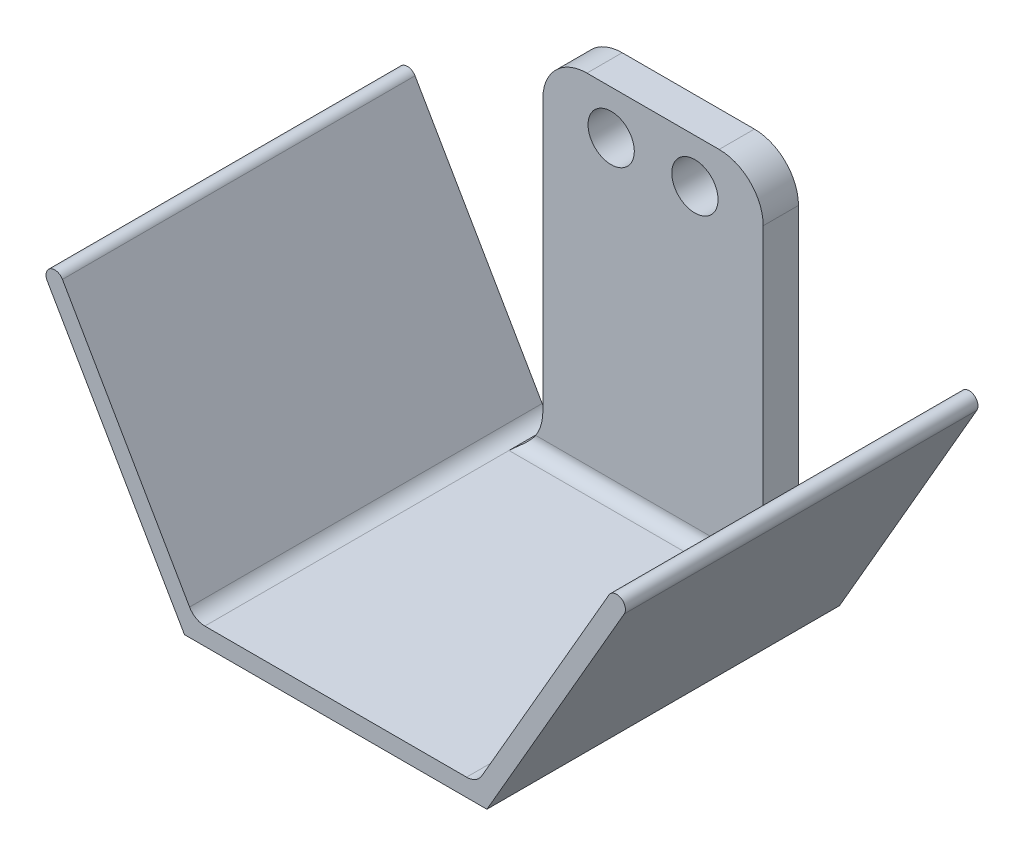
SolidWorks part; units mm, degrees
ref_plane "Front Plane" through (0, 0, 0) normal (0, 0, 1) x (1, 0, 0)
ref_plane "Top Plane" through (0, 0, 0) normal (0, 1, 0) x (1, 0, 0)
ref_plane "Right Plane" through (0, 0, 0) normal (1, 0, 0) x (0, 0, -1)
sketch "Sketch2" plane through (0, 0, 0) normal (0, 0, 1) x (1, 0, 0)
  line L0 (-32, 0) -> (32, 0)
  line L1 (32, 0) -> (62, 51.9615)
  line L2 (-32, 0) -> (-62, 51.9615)
  line L3 (-34.3094, -4) -> (-65.4641, 49.9615)
  line L4 (-34.3094, -4) -> (34.3094, -4)
  line L5 (34.3094, -4) -> (65.4641, 49.9615)
  arc A0 (-62, 51.9615) -> (-65.4641, 49.9615) centre (-63.7321, 50.9615) ccw
  arc A1 (62, 51.9615) -> (65.4641, 49.9615) centre (63.7321, 50.9615) cw
  point P4 (0, 0)
  dimension "D1" = 60
  dimension "D2" = 60
  dimension "D3" = 64
  dimension "D4" = 60
  dimension "D5" = 60
  dimension "D6" = 4
extrude "Boss-Extrude2" add sketch "Sketch2" along normal mid plane 80
fillet "Fillet1" radius 4 2 edges at (32, 0, 0) (-32, 0, 0)
sketch "Sketch3" plane through (0, 0, 0) normal (0, 1, 0) x (1, 0, 0)
  line L0 (29.6906, 40) -> (-29.6906, 40) construction
  line L1 (-25, 40) -> (25, 40)
  line L2 (-25, 40) -> (-25, 32)
  line L3 (-25, 32) -> (25, 32)
  line L4 (25, 40) -> (25, 32)
  point P6 (0, 32)
  dimension "D1" = 8
  dimension "D2" = 50
extrude "Boss-Extrude3" add sketch "Sketch3" along normal blind 80
sketch "Sketch4" plane through (0, 0, 0) normal (1, 0, 0) x (0, 0, -1)
  line L1 (40, 0) -> (32, 0) construction
  line L2 (-40, -4) -> (-40, 49.9615) construction
  circle A0 centre (-10, 30) radius 30 construction
  dimension "D1" = 60
sketch "Sketch7" plane through (0, 0, -32) normal (0, 0, 1) x (1, 0, 0)
  line L0 (-25, 80) -> (25, 80) construction
  circle A0 centre (-10, 70) radius 7.5
  circle A1 centre (10, 70) radius 7.5
  dimension "D3" = 15
  dimension "D4" = 15
  dimension "D1" = 10
  dimension "D2" = 20
  dimension "D5" = 10
extrude "Boss-Extrude4" [suppressed] add sketch "Sketch7" along normal blind 10
sketch "Sketch5" plane through (0, 0, -32) normal (0, 0, 1) x (1, 0, 0)
  line L0 (-25, 80) -> (25, 80) construction
  circle A0 centre (-9.5, 70) radius 5.25
  circle A1 centre (9.5, 70) radius 5.25
  dimension "D1" = 10.5
  dimension "D2" = 10.5
  dimension "D4" = 10
  dimension "D5" = 9.5
  dimension "20" = 19
extrude "Cut-Extrude1" cut sketch "Sketch5" against normal through all
fillet "Fillet2" radius 10 4 edges at (25, 0, -36) (25, 80, -36) (-25, 80, -36) (-25, 0, -36)
fillet "Fillet3" radius 3 1 edges at (0, 0, -32)
equation "\"D5@Sketch5\" = \"20@Sketch5\" / 2"
equation "\"D5@Sketch7\"=\"D2@Sketch7\"/2"
